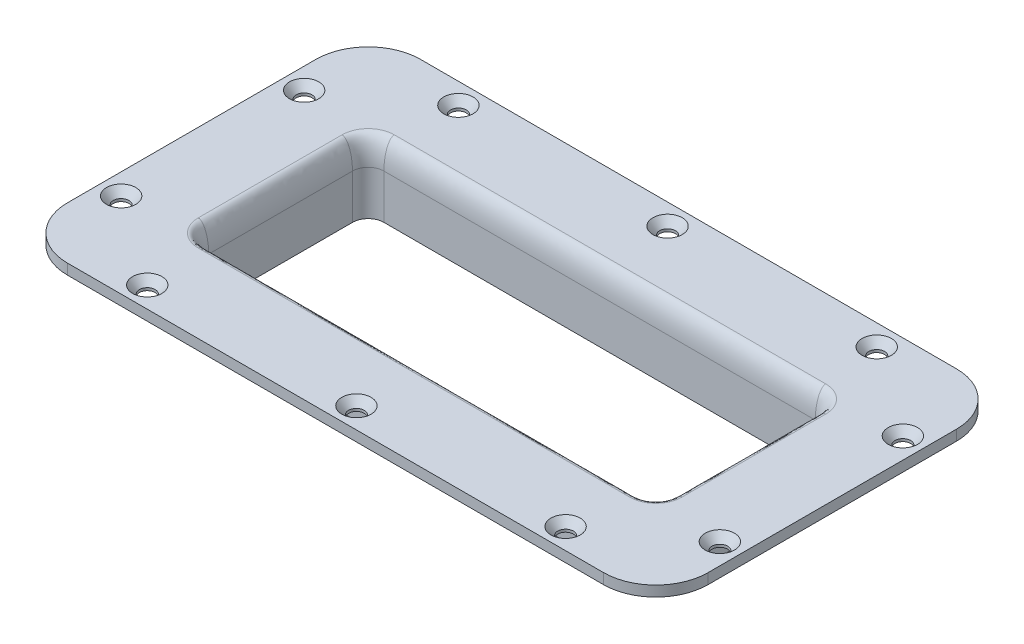
SolidWorks part; units mm, degrees
ref_plane "Front Plane" through (0, 0, 0) normal (0, 0, 1) x (1, 0, 0)
ref_plane "Top Plane" through (0, 0, 0) normal (0, 1, 0) x (1, 0, 0)
ref_plane "Right Plane" through (0, 0, 0) normal (1, 0, 0) x (0, 0, -1)
sketch "Sketch1" plane through (0, 0, 0) normal (0, 1, 0) x (1, 0, 0)
  line L0 (-56.1975, 17.4625) -> (-56.1975, -17.4625)
  line L1 (-52.3875, 23.8125) -> (52.3875, 23.8125)
  line L2 (-58.7375, 17.4625) -> (-58.7375, -17.4625)
  line L3 (-52.3875, -23.8125) -> (52.3875, -23.8125)
  line L4 (58.7375, 17.4625) -> (58.7375, -17.4625)
  line L5 (-58.7375, 23.8125) -> (58.7375, -23.8125) construction
  line L6 (-58.7375, -23.8125) -> (58.7375, 23.8125) construction
  line L7 (-52.3875, -21.2725) -> (52.3875, -21.2725)
  line L8 (56.1975, 17.4625) -> (56.1975, -17.4625)
  line L9 (-52.3875, 21.2725) -> (52.3875, 21.2725)
  arc A0 (52.3875, 23.8125) -> (58.7375, 17.4625) centre (52.3875, 17.4625) cw
  arc A1 (52.3875, -23.8125) -> (58.7375, -17.4625) centre (52.3875, -17.4625) ccw
  arc A2 (-58.7375, -17.4625) -> (-52.3875, -23.8125) centre (-52.3875, -17.4625) ccw
  arc A3 (-52.3875, 23.8125) -> (-58.7375, 17.4625) centre (-52.3875, 17.4625) ccw
  arc A4 (-56.1975, -17.4625) -> (-52.3875, -21.2725) centre (-52.3875, -17.4625) ccw
  arc A5 (52.3875, -21.2725) -> (56.1975, -17.4625) centre (52.3875, -17.4625) ccw
  arc A6 (52.3875, 21.2725) -> (56.1975, 17.4625) centre (52.3875, 17.4625) cw
  arc A7 (-52.3875, 21.2725) -> (-56.1975, 17.4625) centre (-52.3875, 17.4625) ccw
  point P0 (0, 0)
  dimension "D1" = 6.35
  dimension "D2" = 117.475
  dimension "D3" = 47.625
  dimension "D4" = 2.54
extrude "Boss-Extrude1" add sketch "Sketch1" along normal blind 14.605
sketch "Sketch2" plane through (0, 14.605, 0) normal (0, 1, 0) x (1, 0, 0)
  line L0 (52.3875, 23.8125) -> (-52.3875, 23.8125) construction
  line L1 (-65.0875, -42.8625) -> (65.0875, -42.8625)
  line L2 (-77.7875, -30.1625) -> (-77.7875, 30.1625)
  line L3 (-65.0875, 42.8625) -> (65.0875, 42.8625)
  line L4 (77.7875, -30.1625) -> (77.7875, 30.1625)
  line L5 (-77.7875, -42.8625) -> (77.7875, 42.8625) construction
  line L6 (-77.7875, 42.8625) -> (77.7875, -42.8625) construction
  line L7 (-58.7375, 17.4625) -> (-58.7375, -17.4625) construction
  line L12 (-56.1975, 17.4625) -> (-56.1975, -17.4625) construction
  line L13 (-52.3875, -21.2725) -> (52.3875, -21.2725) construction
  line L14 (56.1975, -17.4625) -> (56.1975, 17.4625) construction
  line L15 (52.3875, 21.2725) -> (-52.3875, 21.2725) construction
  line L16 (52.3875, 21.2725) -> (-52.3875, 21.2725)
  line L17 (56.1975, -17.4625) -> (56.1975, 17.4625)
  line L18 (-52.3875, -21.2725) -> (52.3875, -21.2725)
  line L19 (-56.1975, 17.4625) -> (-56.1975, -17.4625)
  arc A0 (65.0875, 42.8625) -> (77.7875, 30.1625) centre (65.0875, 30.1625) cw
  arc A1 (65.0875, -42.8625) -> (77.7875, -30.1625) centre (65.0875, -30.1625) ccw
  arc A2 (-65.0875, -42.8625) -> (-77.7875, -30.1625) centre (-65.0875, -30.1625) cw
  arc A3 (-77.7875, 30.1625) -> (-65.0875, 42.8625) centre (-65.0875, 30.1625) cw
  arc A12 (52.3875, -21.2725) -> (56.1975, -17.4625) centre (52.3875, -17.4625) ccw construction
  arc A13 (56.1975, 17.4625) -> (52.3875, 21.2725) centre (52.3875, 17.4625) ccw construction
  arc A14 (-52.3875, 21.2725) -> (-56.1975, 17.4625) centre (-52.3875, 17.4625) ccw construction
  arc A15 (-52.3875, 21.2725) -> (-56.1975, 17.4625) centre (-52.3875, 17.4625) ccw
  arc A20 (56.1975, 17.4625) -> (52.3875, 21.2725) centre (52.3875, 17.4625) ccw
  arc A21 (52.3875, -21.2725) -> (56.1975, -17.4625) centre (52.3875, -17.4625) ccw
  arc A22 (-56.1975, -17.4625) -> (-52.3875, -21.2725) centre (-52.3875, -17.4625) ccw construction
  arc A23 (-56.1975, -17.4625) -> (-52.3875, -21.2725) centre (-52.3875, -17.4625) ccw
  point P0 (0, 0)
  dimension "D3" = 12.7
  dimension "D1" = 19.05
  dimension "D2" = 19.05
extrude "Boss-Extrude2" add sketch "Sketch2" along normal blind 2.54
fillet "Fillet1" radius 5.715 8 edges at (-56.8776, 14.605, -21.9526) (0, 14.605, -23.8125) (56.8776, 14.605, -21.9526) (58.7375, 14.605, 0) (56.8776, 14.605, 21.9526) (0, 14.605, 23.8125) (-56.8776, 14.605, 21.9526) (-58.7375, 14.605, 0)
fillet "Fillet3" radius 2.54 8 edges at (0, 17.145, 21.2725) (55.0816, 17.145, 20.1566) (-55.0816, 17.145, 20.1566) (56.1975, 17.145, 0) (-56.1975, 17.145, 0) (55.0816, 17.145, -20.1566) (-55.0816, 17.145, -20.1566) (0, 17.145, -21.2725) second distance 6.35 first distance on face at (0, 17.145, 0)
sketch "Sketch3" plane through (0, 17.145, 0) normal (0, 1, 0) x (1, 0, 0)
  line L4 (-55, 0) -> (55, 0) construction
  line L5 (0, -55) -> (0, 55) construction
  line L8 (65.0875, 37.7825) -> (-65.0875, 37.7825)
  line L9 (-72.7075, 30.1625) -> (-72.7075, -30.1625)
  line L10 (-65.0875, -37.7825) -> (65.0875, -37.7825)
  line L11 (72.7075, -30.1625) -> (72.7075, 30.1625)
  line L12 (65.0875, 37.7825) -> (-65.0875, 37.7825)
  line L13 (-72.7075, 30.1625) -> (-72.7075, -30.1625)
  line L14 (-65.0875, -37.7825) -> (65.0875, -37.7825)
  line L15 (72.7075, -30.1625) -> (72.7075, 30.1625)
  arc A8 (72.7075, 30.1625) -> (65.0875, 37.7825) centre (65.0875, 30.1625) ccw
  arc A9 (-65.0875, 37.7825) -> (-72.7075, 30.1625) centre (-65.0875, 30.1625) ccw
  arc A10 (-72.7075, -30.1625) -> (-65.0875, -37.7825) centre (-65.0875, -30.1625) ccw
  arc A11 (65.0875, -37.7825) -> (72.7075, -30.1625) centre (65.0875, -30.1625) ccw
  arc A12 (72.7075, 30.1625) -> (65.0875, 37.7825) centre (65.0875, 30.1625) ccw
  arc A13 (-65.0875, 37.7825) -> (-72.7075, 30.1625) centre (-65.0875, 30.1625) ccw
  arc A14 (-72.7075, -30.1625) -> (-65.0875, -37.7825) centre (-65.0875, -30.1625) ccw
  arc A15 (65.0875, -37.7825) -> (72.7075, -30.1625) centre (65.0875, -30.1625) ccw
  point P0 (-72.7075, -22.225)
  point P1 (-50.8, -37.7825)
  point P2 (0, -37.7825)
  point P3 (50.8, -37.7825)
  point P4 (-72.7075, 22.225)
  point P8 (50.8, 37.7825)
  point P9 (-50.8, 37.7825)
  point P10 (0, 37.7825)
  point P15 (72.7075, 22.225)
  point P16 (72.7075, -22.225)
  dimension "D2" = 50.8
  dimension "D3" = 50.8
  dimension "D4" = 44.45
  dimension "D5" = 22.225
  dimension "D1" = 5.08
sketch "Sketch4" plane through (0, 17.145, 0) normal (0, 1, 0) x (1, 0, 0)
  line L0 (65.0875, 37.7825) -> (-65.0875, 37.7825) construction
  line L1 (-65.0875, -37.7825) -> (65.0875, -37.7825) construction
  circle A0 centre (-72.7075, -22.225) radius 1.905
  circle A1 centre (-72.7075, 22.225) radius 1.905
  circle A2 centre (-50.8, 37.7825) radius 1.905
  circle A3 centre (0, 37.7825) radius 1.905
  circle A4 centre (50.8, 37.7825) radius 1.905
  circle A5 centre (72.7075, 22.225) radius 1.905
  circle A6 centre (72.7075, -22.225) radius 1.905
  circle A7 centre (50.8, -37.7825) radius 1.905
  circle A8 centre (0, -37.7825) radius 1.905
  circle A9 centre (-50.8, -37.7825) radius 1.905
  dimension "D1" = 3.81
extrude "Cut-Extrude1" cut sketch "Sketch4" against normal through all
chamfer "Chamfer1" distance 1.651 angle 49 10 edges at (50.8, 17.145, 39.6875) (72.7075, 17.145, 24.13) (72.7075, 17.145, -20.32) (50.8, 17.145, -35.8775) (0, 17.145, -35.8775) (-50.8, 17.145, -35.8775) (-72.7075, 17.145, -20.32) (0, 17.145, 39.6875) (-50.8, 17.145, 39.6875) (-72.7075, 17.145, 24.13) first distance on face at (0, 17.145, 39.6875)
sketch "Sketch5" plane through (0, 0, 21.2725) normal (0, 0, -1) x (-1, 0, 0)
  line L0 (-41.4287, 1.27) -> (41.4287, 1.27) construction
  line L1 (52.3875, 0) -> (-52.3875, 0) construction
  text T0 "<b>Floor Border Seat V2</b>" font "Century Gothic" height 5.08
  point P2 (0, 1.27)
  point P3 (0, 0)
  dimension "D1" = 1.27
extrude "Cut-Extrude2" cut sketch "Sketch5" against normal blind 0.635
